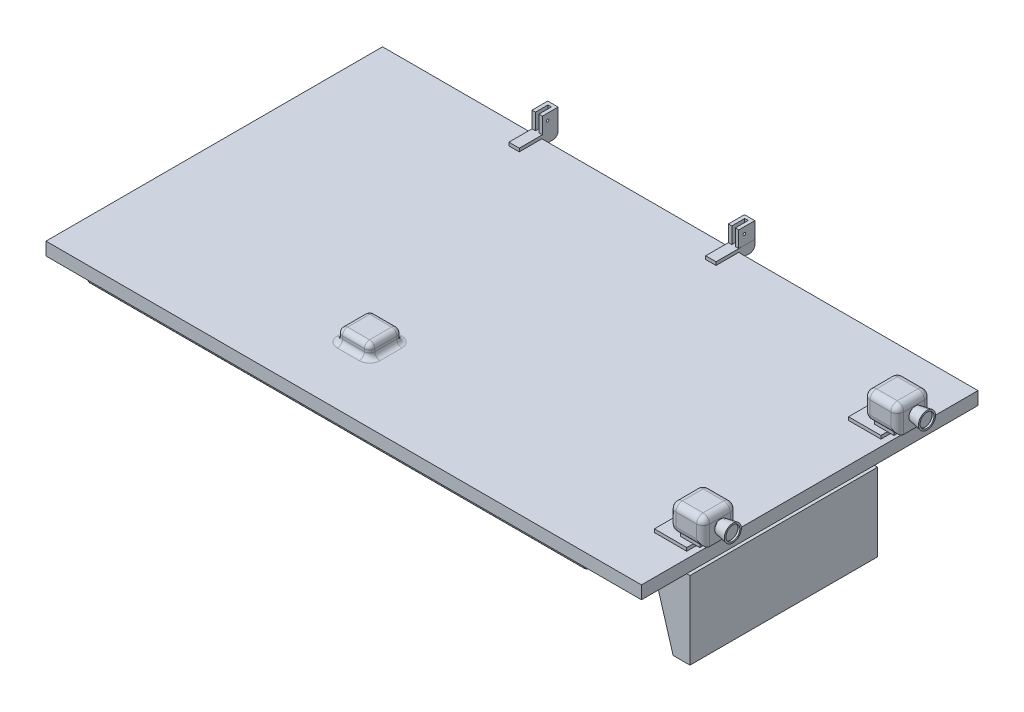
SolidWorks part; units mm, degrees
ref_plane "Front Plane" through (0, 0, 0) normal (0, 0, 1) x (1, 0, 0)
ref_plane "Top Plane" through (0, 0, 0) normal (0, 1, 0) x (1, 0, 0)
ref_plane "Right Plane" through (0, 0, 0) normal (1, 0, 0) x (0, 0, -1)
sketch "Sketch1" plane through (0, 0, 0) normal (0, 1, 0) x (1, 0, 0)
  line L5 (-490.2341, -260) -> (429.7659, -260)
  line L6 (-490.2341, -260) -> (-490.2341, 260)
  line L7 (-490.2341, 260) -> (429.7659, 260)
  line L8 (429.7659, -260) -> (429.7659, 260)
  point P0 (0, 0)
  dimension "D1" = 920
  dimension "D2" = 520
extrude "Boss-Extrude1" add sketch "Sketch1" along normal blind 20
sketch "Sketch3" plane through (0, 0, 0) normal (0, -1, 0) x (1, 0, 0)
  line L0 (429.7659, 260) -> (429.7659, -260) construction
  line L3 (-450.2341, 235) -> (319.7659, 235)
  line L4 (-450.2341, 235) -> (-450.2341, -235)
  line L5 (-450.2341, -235) -> (319.7659, -235)
  line L6 (319.7659, 235) -> (319.7659, -235)
  line L7 (-450.2341, 235) -> (319.7659, -235) construction
  line L8 (-450.2341, -235) -> (319.7659, 235) construction
  line L9 (-440.2341, 225) -> (309.7659, 225)
  line L10 (-440.2341, 225) -> (-440.2341, -225)
  line L11 (-440.2341, -225) -> (309.7659, -225)
  line L12 (309.7659, 225) -> (309.7659, -225)
  line L13 (-440.2341, 225) -> (309.7659, -225) construction
  line L14 (-440.2341, -225) -> (309.7659, 225) construction
  line L15 (-490.2341, -260) -> (-490.2341, 260) construction
  point P4 (-65.2341, 0)
  point P11 (-65.2341, 0)
  point P16 (-65.2341, -235)
  dimension "D4" = 225
  dimension "D5" = 10
  dimension "D6" = 10
  dimension "D7" = 10
  dimension "D8" = 225
  dimension "D9" = 10
  dimension "D10" = 40
  dimension "D11" = 110
extrude "Boss-Extrude2" add sketch "Sketch3" along normal blind 30
sketch "Sketch4" plane through (0, 0, 0) normal (0, -1, 0) x (-1, 0, 0)
  line L0 (-319.7659, 235) -> (-319.7659, -235) construction
  line L1 (450.2341, 235) -> (-319.7659, 235) construction
  line L4 (450.2341, -235) -> (450.2341, 235) construction
  line L5 (-319.7659, -235) -> (450.2341, -235) construction
  circle A0 centre (-239.7659, 0) radius 25
  circle A1 centre (300.2341, -175) radius 25
  circle A2 centre (300.2341, 175) radius 25
  dimension "D1" = 80
  dimension "D2" = 235
  dimension "D3" = 50
  dimension "D4" = 50
  dimension "D5" = 50
  dimension "D6" = 150
  dimension "D7" = 150
  dimension "D8" = 60
  dimension "D9" = 60
extrude "Cut-Extrude1" cut sketch "Sketch4" against normal blind 10
sketch "Sketch6" plane through (0, 10, 0) normal (0, -1, 0) x (1, 0, 0)
  circle A0 centre (239.7659, 0) radius 25
  circle A1 centre (239.7659, 0) radius 30
  circle A2 centre (-300.2341, 175) radius 25
  circle A3 centre (-300.2341, 175) radius 30
  circle A4 centre (-300.2341, -175) radius 25
  circle A5 centre (-300.2341, -175) radius 30
  circle A6 centre (239.7659, 0) radius 25 construction
  circle A7 centre (-300.2341, -175) radius 25 construction
  circle A8 centre (-300.2341, 175) radius 25 construction
  dimension "D1" = 50
  dimension "D2" = 60
extrude "Boss-Extrude4" add sketch "Sketch6" along normal blind 15
sketch "Sketch7" plane through (0, 20, 0) normal (0, 1, 0) x (1, 0, 0)
  line L1 (60, 225) -> (44, 225)
  line L2 (60, 225) -> (60, 285)
  line L3 (60, 285) -> (44, 285)
  line L4 (44, 225) -> (44, 285)
  line L5 (60, 225) -> (44, 285) construction
  line L6 (60, 285) -> (44, 225) construction
  line L7 (-244, 225) -> (-260, 225)
  line L8 (-244, 225) -> (-244, 285)
  line L9 (-244, 285) -> (-260, 285)
  line L10 (-260, 225) -> (-260, 285)
  line L11 (-244, 225) -> (-260, 285) construction
  line L12 (-244, 285) -> (-260, 225) construction
  line L14 (429.7659, 260) -> (-490.2341, 260) construction
  point P0 (-252, 255)
  dimension "D1" = 16
  dimension "D2" = 16
  dimension "D3" = 288
  dimension "D5" = 35
  dimension "D6" = 25
  dimension "D7" = 60
  dimension "D8" = 25
extrude "Boss-Extrude5" add sketch "Sketch7" along normal blind 5 and the other way blind 10
fillet "Fillet1" radius 8 2 edges at (-252, 10, -285) (52, 10, -285)
sketch "Sketch10" plane through (0, 25, 0) normal (0, 1, 0) x (1, 0, 0)
  line L0 (-249.3, 280.0282) -> (-249.3, 260.7014)
  line L1 (-260, 285) -> (-254.5695, 285)
  line L2 (-260, 285) -> (-260, 260.7014)
  line L3 (-260, 260.7014) -> (-254.7, 260.7014)
  line L4 (-244, 285) -> (-244, 260.7014)
  line L6 (-254.7, 260.7014) -> (-254.7, 280.0282)
  line L7 (-249.8297, 285) -> (-244, 285)
  line L19 (-249.3, 260.7014) -> (-244, 260.7014)
  line L20 (43.9451, 260.1609) -> (43.9451, 285.0164)
  line L21 (-249.8297, 285) -> (-254.5695, 285)
  line L23 (-249.3, 280.0282) -> (-254.7, 280.0282)
  line L24 (43.9451, 285.0164) -> (60.0067, 285.0164)
  line L25 (60.0067, 285.0164) -> (59.9451, 260.1609)
  line L26 (59.9451, 260.1609) -> (54.6451, 260.1609)
  line L27 (54.6451, 260.1609) -> (54.6451, 280.0446)
  line L28 (54.6451, 280.0446) -> (49.2451, 280.0446)
  line L29 (49.2451, 280.0446) -> (49.2451, 260.1609)
  line L30 (49.2451, 260.1609) -> (43.9451, 260.1609)
  dimension "D1" = 4.9718
  dimension "D2" = 4.9718
  dimension "D3" = 5.4
  dimension "D4" = 5.3
  dimension "D5" = 5.3
  dimension "D6" = 5.3
  dimension "D7" = 5.4
extrude "Boss-Extrude6" add sketch "Sketch10" along normal blind 25
sketch "Sketch11" plane through (-260, 0, 0) normal (-1, 0, 0) x (0, 0, 1)
  line L0 (-285, 50) -> (-260.7014, 50) construction
  line L1 (-260.7014, 50) -> (-260.7014, 25) construction
  circle A0 centre (-268.7014, 40) radius 2
  dimension "D1" = 10
  dimension "D2" = 8
  dimension "D3" = 4
extrude "Cut-Extrude4" cut sketch "Sketch11" against normal blind 335
sketch "Sketch12" plane through (0, 20, 0) normal (0, 1, 0) x (1, 0, 0)
  line L0 (-490.2341, 260) -> (-490.2341, -260) construction
  line L1 (-130.2341, -170) -> (-80.2341, -170)
  line L2 (-130.2341, -170) -> (-130.2341, -120)
  line L3 (-130.2341, -120) -> (-80.2341, -120)
  line L4 (-80.2341, -170) -> (-80.2341, -120)
  line L5 (-490.2341, -260) -> (429.7659, -260) construction
  dimension "D1" = 50
  dimension "D2" = 50
  dimension "D3" = 360
  dimension "D4" = 90
extrude "Boss-Extrude7" add sketch "Sketch12" along normal blind 20
sketch "Sketch14" plane through (0, 0, 0) normal (0, -1, 0) x (1, 0, 0)
  line L0 (-490.2341, 260) -> (429.7659, 260) construction
  line L1 (428.7057, 100) -> (348.7057, 100)
  line L2 (428.7057, 100) -> (428.7057, -100)
  line L3 (428.7057, -100) -> (348.7057, -100)
  line L4 (348.7057, 100) -> (348.7057, -100)
  dimension "D1" = 200
  dimension "D2" = 160
  dimension "D3" = 80
extrude "Boss-Extrude9" add sketch "Sketch14" along normal blind 40
sketch "Sketch15" plane through (428.7057, 0, 0) normal (1, 0, 0) x (0, 0, -1)
  line L0 (-260, 20) -> (-260, 0) construction
  line L1 (100, 0) -> (-190, 0)
  line L2 (100, 0) -> (100, -120)
  line L3 (100, -120) -> (-190, -120)
  line L4 (-190, 0) -> (-190, -120)
  line L5 (100, -40) -> (100, 0) construction
  line L6 (100, -40) -> (-100, -40) construction
  line L9 (-260, 0) -> (260, 0) construction
  dimension "D1" = 70
  dimension "D2" = 0
  dimension "D3" = 80
extrude "Boss-Extrude10" add sketch "Sketch15" along normal blind 6
sketch "Sketch16" plane through (0, 20, 0) normal (0, 1, 0) x (1, 0, 0)
  line L0 (-490.2341, -260) -> (429.7659, -260) construction
  line L1 (419.7659, -180) -> (369.7659, -180)
  line L2 (419.7659, -180) -> (419.7659, -120)
  line L3 (419.7659, -120) -> (369.7659, -120)
  line L4 (369.7659, -180) -> (369.7659, -120)
  line L5 (419.7659, 120) -> (369.7659, 120)
  line L6 (419.7659, 120) -> (419.7659, 180)
  line L7 (419.7659, 180) -> (369.7659, 180)
  line L8 (369.7659, 120) -> (369.7659, 180)
  line L9 (429.7659, 260) -> (60, 260) construction
  line L10 (429.7659, -260) -> (429.7659, 260) construction
  dimension "D1" = 60
  dimension "D2" = 50
  dimension "D3" = 50
  dimension "D4" = 60
  dimension "D5" = 80
  dimension "D6" = 80
  dimension "D7" = 10
  dimension "D8" = 10
extrude "Boss-Extrude11" add sketch "Sketch16" along normal blind 5
sketch "Sketch17" plane through (0, 25, 0) normal (0, 1, 0) x (1, 0, 0)
  line L0 (400, -130) -> (400, -170)
  line L1 (400, -170) -> (430, -170)
  line L2 (430, -170) -> (430, -130)
  line L3 (430, -130) -> (400, -130)
  line L20 (400, 170) -> (400, 130)
  line L21 (400, 130) -> (430, 130)
  line L22 (430, 130) -> (430, 170)
  line L23 (430, 170) -> (400, 170)
extrude "Boss-Extrude12" add sketch "Sketch17" along normal blind 5
sketch "Sketch18" plane through (0, 30, 0) normal (0, 1, 0) x (1, 0, 0)
  line L4 (400, -170) -> (430, -170) construction
  line L5 (430, -130) -> (400, -130) construction
  line L6 (400, 130) -> (430, 130) construction
  line L20 (441, 176) -> (389, 176)
  line L21 (389, 176) -> (389, 124)
  line L22 (389, 124) -> (441, 124)
  line L23 (441, 124) -> (441, 176)
  line L24 (441, -124) -> (389, -124)
  line L25 (389, -124) -> (389, -176)
  line L26 (389, -176) -> (441, -176)
  line L27 (441, -176) -> (441, -124)
  dimension "D1" = 52
  dimension "D2" = 6
  dimension "D3" = 6
  dimension "D4" = 6
  dimension "D5" = 52
extrude "Boss-Extrude13" add sketch "Sketch18" along normal blind 40
sketch "Sketch19" plane through (441, 0, 0) normal (1, 0, 0) x (0, 0, -1)
  line L0 (-124, 70) -> (-124, 30) construction
  line L1 (-176, 70) -> (-176, 30) construction
  line L2 (-176, 70) -> (-124, 70) construction
  line L3 (124, 70) -> (124, 30) construction
  line L4 (124, 70) -> (176, 70) construction
  circle A0 centre (-150, 51) radius 7.5
  circle A1 centre (150, 51) radius 7.5
  point P4 (-150, 52.3514)
  dimension "D1" = 26
  dimension "D2" = 26
  dimension "D3" = 15
  dimension "D4" = 15
  dimension "D5" = 26
  dimension "D6" = 19
  dimension "D7" = 19
extrude "Boss-Extrude14" add sketch "Sketch19" along normal blind 2
sketch "Sketch20" plane through (443, 0, 0) normal (1, 0, 0) x (0, 0, -1)
  line L0 (-176, 70) -> (-176, 30) construction
  line L1 (-176, 70) -> (-124, 70) construction
  line L2 (-176, 30) -> (-124, 30) construction
  line L3 (-124, 70) -> (-124, 30) construction
  line L4 (124, 70) -> (176, 70) construction
  circle A0 centre (-150, 50) radius 10
  circle A5 centre (150, 51) radius 10
  point P2 (-150, 60.7208)
  point P3 (-150, 60.7208)
  point P4 (-149.8581, 51.491)
  point P6 (0, 0)
  dimension "D1" = 20
  dimension "D2" = 20
  dimension "D3" = 26
  dimension "D4" = 20
  dimension "D5" = 20
  dimension "D6" = 26
  dimension "D7" = 19
extrude "Boss-Extrude15" add sketch "Sketch20" along normal blind 18 draft 10 draft outward yes
sketch "Sketch21" plane through (0, 0, 190) normal (0, 0, 1) x (1, 0, 0)
  line L0 (428.7057, -120) -> (408.7057, -120)
  line L1 (408.7057, -120) -> (384.8562, -40)
  line L2 (428.7057, -40) -> (348.7057, -40) construction
  line L3 (384.8562, -40) -> (428.7057, -40)
  line L4 (428.7057, -40) -> (428.7057, -120)
  line L5 (428.7057, 0) -> (428.7057, -120) construction
  dimension "D1" = 20
extrude "Boss-Extrude16" add sketch "Sketch21" against normal blind 289
sketch "Sketch22" plane through (0, 0, 190) normal (0, 0, 1) x (1, 0, 0)
  line L0 (-490.2341, 0) -> (429.7659, 0) construction
  line L1 (428.7057, -40) -> (384.8562, -40)
  line L2 (428.7057, -40) -> (428.7057, 0)
  line L3 (428.7057, 0) -> (384.8562, 0)
  line L4 (384.8562, -40) -> (384.8562, 0)
extrude "Boss-Extrude17" add sketch "Sketch22" against normal blind 110
fillet "Fillet2" radius 10 22 edges at (389, 30, 150) (441, 50, -124) (415, 30, -124) (389, 50, -124) (389, 30, -150) (415, 70, -124) (389, 70, -150) (441, 70, -150) (441, 50, -176) (415, 70, -176) (389, 50, -176) (415, 30, -176) (389, 70, 150) (441, 70, 150) (441, 50, 124) (415, 70, 124) (389, 50, 124) (415, 30, 124) (389, 50, 176) (415, 70, 176) (441, 50, 176) (415, 30, 176)
sketch "Sketch23" plane through (461, 0, 0) normal (1, 0, 0) x (0, 0, -1)
  circle A0 centre (-150, 50) radius 10.7363
  circle A1 centre (-150, 50) radius 13.1739 construction
  circle A2 centre (150, 51) radius 10.7363
  circle A3 centre (150, 51) radius 13.1739 construction
  point P4 (0, 0)
  point P5 (0, 0)
  point P8 (0, 0)
extrude "Cut-Extrude5" cut sketch "Sketch23" against normal blind 3
fillet "Fillet4" radius 8 12 edges at (-105.2341, 40, 120) (-80.2341, 40, 145) (-105.2341, 40, 170) (-130.2341, 40, 145) (-130.2341, 20, 145) (-130.2341, 30, 120) (-105.2341, 20, 120) (-80.2341, 30, 120) (-80.2341, 20, 145) (-130.2341, 30, 170) (-80.2341, 30, 170) (-105.2341, 20, 170)
fillet "Fillet12" radius 5 13 edges at (-65.2341, 0, -235) (-65.2341, 0, 235) (319.7659, -15, -235) (319.7659, -15, 235) (319.7659, 0, 0) (-440.2341, -30, 0) (-65.2341, -30, -225) (309.7659, -30, 0) (-65.2341, -30, 225) (-65.2341, -30, -235) (-450.2341, -30, 0) (-65.2341, -30, 235) (319.7659, -30, 0)
